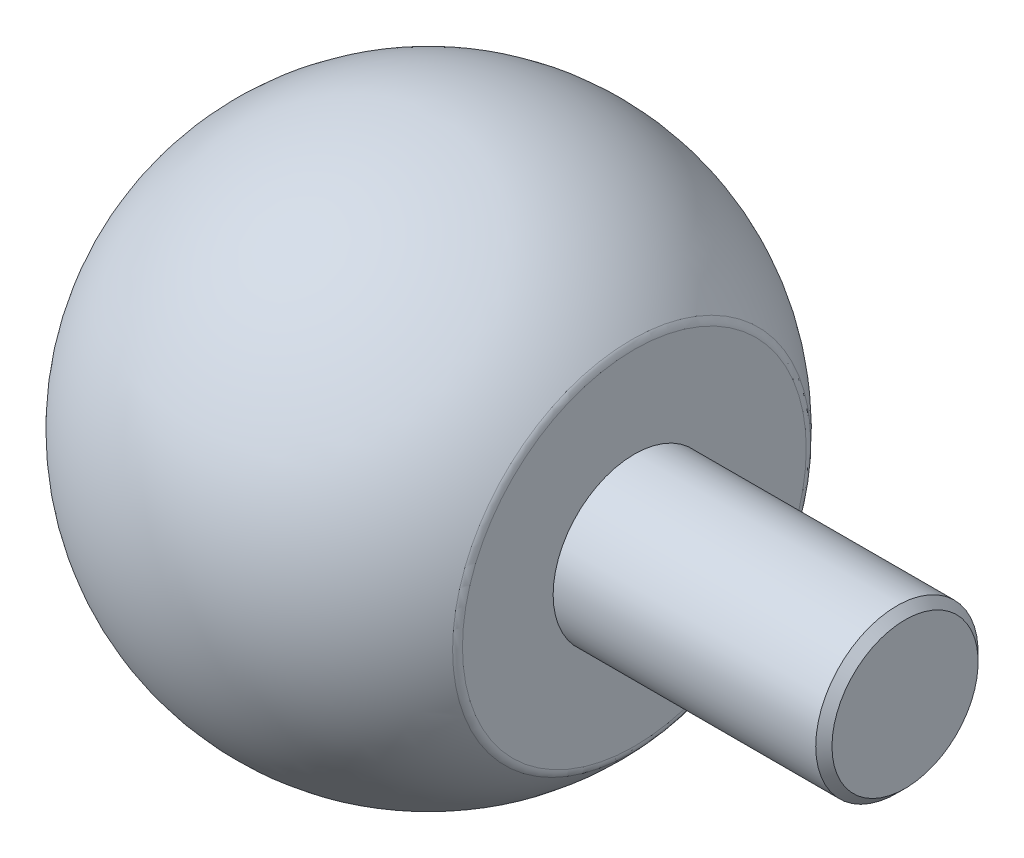
SolidWorks part; units mm, degrees
ref_plane "前视基准面" through (0, 0, 0) normal (0, 0, 1) x (1, 0, 0)
ref_plane "上视基准面" through (0, 0, 0) normal (0, 1, 0) x (1, 0, 0)
ref_plane "右视基准面" through (0, 0, 0) normal (1, 0, 0) x (0, 0, -1)
sketch "草图1" plane through (0, 0, 0) normal (0, 0, 1) x (1, 0, 0)
  line L0 (0, 5) -> (0, -5)
  arc A0 (0, -5) -> (0, 5) centre (0, 0) ccw
ref_plane "基准面1" through (2.9747, 0, 0) normal (1, 0, 0) x (0, 0, -1)
sketch "草图5" plane through (0, 0, 0) normal (0, 0, 1) x (1, 0, 0)
  line L0 (0, 0) -> (-3.3324, -49.5269)
  line L1 (-0.3162, -4.7) -> (6.1291, -5.1337)
ref_plane "基准面2" through (-0.3162, -4.7, 0) normal (-0.0671, -0.9977, 0) x (0.9977, -0.0671, 0)
sketch "草图6" plane through (-0.3162, -4.7, 0) normal (-0.0671, -0.9977, 0) x (0.9977, -0.0671, 0)
  circle A0 centre (0, 0) radius 2
revolve "旋转1" add sketch "草图1" angle 360 about L0
extrude "切除-拉伸1" cut sketch "草图6" against normal blind 0.2
extrude "切除-拉伸2" cut sketch "草图6<2>" along normal blind 5
sketch "草图6<2>" plane through (-0.3162, -4.7, 0) normal (-0.0671, -0.9977, 0) x (0.9977, -0.0671, 0) same geometry as "草图6"
hole_wizard "M3 螺纹孔1" positions "3D草图3" profile "草图9" tap size "M3" standard "GB"
sketch3d "3D草图3"
  line L0 (-0.3028, -4.5005, 0) -> (-0.3076, -4.5722, 0) construction
  point P0 (-0.3028, -4.5005, 0)
sketch "草图9" plane through (-0.3028, -4.5005, 0) normal (0, 0, 1) x (0.9977, -0.0671, 0)
  line L0 (0, 0) -> (0, 6.2511)
  line L1 (0, 6.2511) -> (1.25, 5.5)
  line L2 (1.25, 5.5) -> (1.25, 0)
  line L5 (1.25, 0) -> (0, 0)
  line L10 (0, 6.2511) -> (-1.25, 5.5) construction
  line L11 (0, -6.35) -> (0, 107.95) construction
  dimension "螺纹孔钻头直径" = 2.5
  dimension "螺纹孔钻头深度" = 5.5
  dimension "导头角度" = 118
cosmetic thread "孔螺蚊线1" parameters "D1"=3, "D2"=3
ref_plane "基准面3" through (3.8, 0, 0) normal (1, 0, 0) x (0, 0, -1)
sketch "草图10" plane through (3.8, 0, 0) normal (1, 0, 0) x (0, 0, -1)
  circle A0 centre (0, 0) radius 10.599
extrude "切除-拉伸3" cut sketch "草图10" along normal blind 10
sketch "草图11" plane through (3.8, 0, 0) normal (1, 0, 0) x (0, 0, -1)
  circle A0 centre (0, 0) radius 1.5
extrude "凸台-拉伸1" add sketch "草图11" along normal blind 5
cosmetic thread "装饰螺纹线1" parameters "D2"=2.459
fillet "圆角1" radius 0.2 1 edges at (3.8, 0, -3.2496)
chamfer "倒角1" distance 0.15 angle 45 1 edges at (8.8, 0, -1.5)
